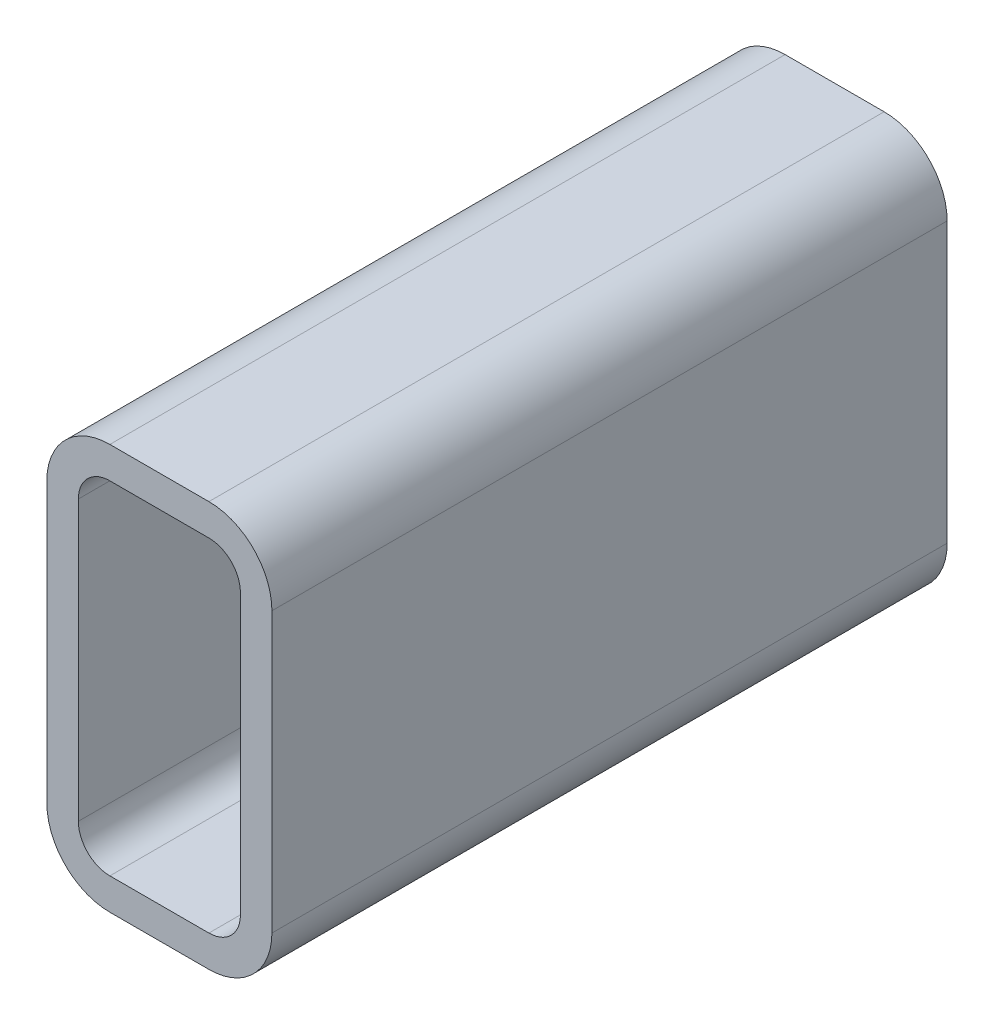
SolidWorks part; units mm, degrees
material "普通碳钢"
ref_plane "前视基准面" through (0, 0, 0) normal (0, 0, 1) x (1, 0, 0)
ref_plane "上视基准面" through (0, 0, 0) normal (0, 1, 0) x (1, 0, 0)
ref_plane "右视基准面" through (0, 0, 0) normal (1, 0, 0) x (0, 0, -1)
ref_plane "基准面" through (0, 0, 0) normal (0, 0, 1) x (1, 0, 0)
sketch "草图1" plane through (0, 0, 0) normal (0, 0, 1) x (1, 0, 0)
  line L0 (0, 0) -> (15.3811, 0) construction
  line L1 (-50, 90) -> (50, 90)
  line L2 (-50, 90) -> (-50, -90)
  line L3 (-50, -90) -> (50, -90)
  line L4 (50, 90) -> (50, -90)
  line L5 (-36, 76) -> (36, 76)
  line L6 (-36, 76) -> (-36, -76)
  line L7 (-36, -76) -> (36, -76)
  line L8 (36, 76) -> (36, -76)
  line L9 (0, 0) -> (0, 19.6754) construction
  point P11 (0, 40)
  point P13 (0, 0)
  point P15 (0, 0)
  point P16 (0, -40)
  dimension "D1" = 180
  dimension "D3" = 14
  dimension "D2" = 100
  dimension "D4" = 14
  dimension "D5" = 80
extrude "凸台-拉伸1" add sketch "草图1" along normal blind 300
ref_axis "中心轴" through (0, 0, 0) along (0, 0, 1)
ref_axis "中心轴L" through (0, 40, 0) along (0, 0, 1)
ref_axis "中心轴R" through (0, -40, 0) along (0, 0, 1)
fillet "圆角1" radius 14 4 edges at (-36, -76, 150) (-36, 76, 150) (36, 76, 150) (36, -76, 150)
fillet "圆角2" radius 28 4 edges at (-50, -90, 150) (50, -90, 150) (-50, 90, 150) (50, 90, 150)
